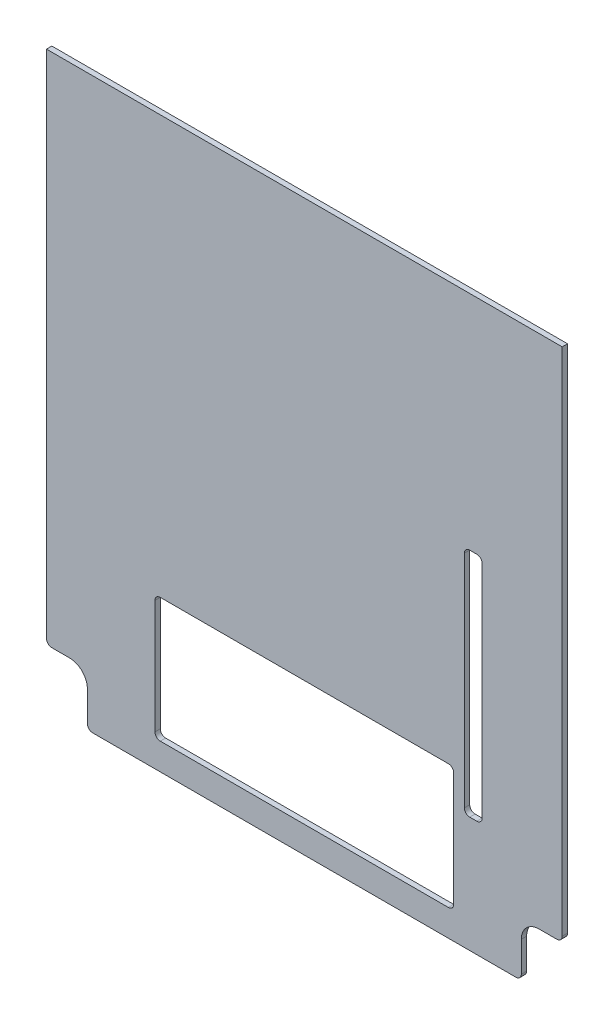
SolidWorks part; units mm, degrees
ref_plane "Front" through (0, 0, 0) normal (0, 0, 1) x (1, 0, 0)
ref_plane "Top" through (0, 0, 0) normal (0, 1, 0) x (1, 0, 0)
ref_plane "Right" through (0, 0, 0) normal (1, 0, 0) x (0, 0, -1)
sketch "Esquisse1" plane through (0, 0, 0) normal (0, 0, 1) x (1, 0, 0)
  line L1 (0, 0) -> (290, 0)
  line L2 (0, 0) -> (0, 320)
  line L3 (0, 320) -> (290, 320)
  line L4 (290, 0) -> (290, 320)
  dimension "D1" = 290
  dimension "D2" = 320
extrude "Boss.-Extru.1" add sketch "Esquisse1" along normal blind 3
sketch "Esquisse2" plane through (0, 0, 3) normal (0, 0, 1) x (1, 0, 0)
  line L0 (145, 0) -> (145, 172.6222) construction
  line L1 (290, 0) -> (267, 0)
  line L2 (290, 0) -> (290, 30)
  line L3 (290, 30) -> (267, 30)
  line L4 (267, 0) -> (267, 30)
  line L5 (0, 0) -> (290, 0) construction
  line L6 (23, 0) -> (23, 30)
  line L7 (0, 30) -> (23, 30)
  line L8 (0, 0) -> (0, 30)
  line L9 (0, 0) -> (23, 0)
  dimension "D1" = 23
  dimension "D2" = 30
extrude "Enlèv. mat.-Extru.1" cut sketch "Esquisse2" against normal through all both and the other way through all
fillet "Congé1" radius 10 2 edges at (23, 30, 1.5) (267, 30, 1.5)
fillet "Congé2" radius 3 4 edges at (267, 0, 1.5) (290, 30, 1.5) (23, 0, 1.5) (0, 30, 1.5)
sketch "Esquisse3" plane through (0, 0, 3) normal (0, 0, 1) x (1, 0, 0)
  line L0 (26, 0) -> (264, 0) construction
  line L1 (235, 195) -> (245, 195)
  line L2 (235, 195) -> (235, 65)
  line L3 (235, 65) -> (245, 65)
  line L4 (245, 195) -> (245, 65)
  dimension "D1" = 10
  dimension "D2" = 235
  dimension "D3" = 65
  dimension "D4" = 130
extrude "Enlèv. mat.-Extru.2" cut sketch "Esquisse3" against normal through all both and the other way through all
sketch "Esquisse4" plane through (0, 0, 3) normal (0, 0, 1) x (1, 0, 0)
  line L0 (26, 0) -> (264, 0) construction
  line L1 (61, 15) -> (229, 15)
  line L2 (61, 15) -> (61, 85)
  line L3 (61, 85) -> (229, 85)
  line L4 (229, 15) -> (229, 85)
  line L5 (145, 15) -> (145, 0) construction
  dimension "D1" = 70
  dimension "D2" = 15
  dimension "D3" = 168
extrude "Enlèv. mat.-Extru.3" cut sketch "Esquisse4" against normal through all both and the other way through all
fillet "Congé3" radius 3 8 edges at (235, 195, 1.5) (245, 195, 1.5) (245, 65, 1.5) (235, 65, 1.5) (229, 15, 1.5) (229, 85, 1.5) (61, 85, 1.5) (61, 15, 1.5)
